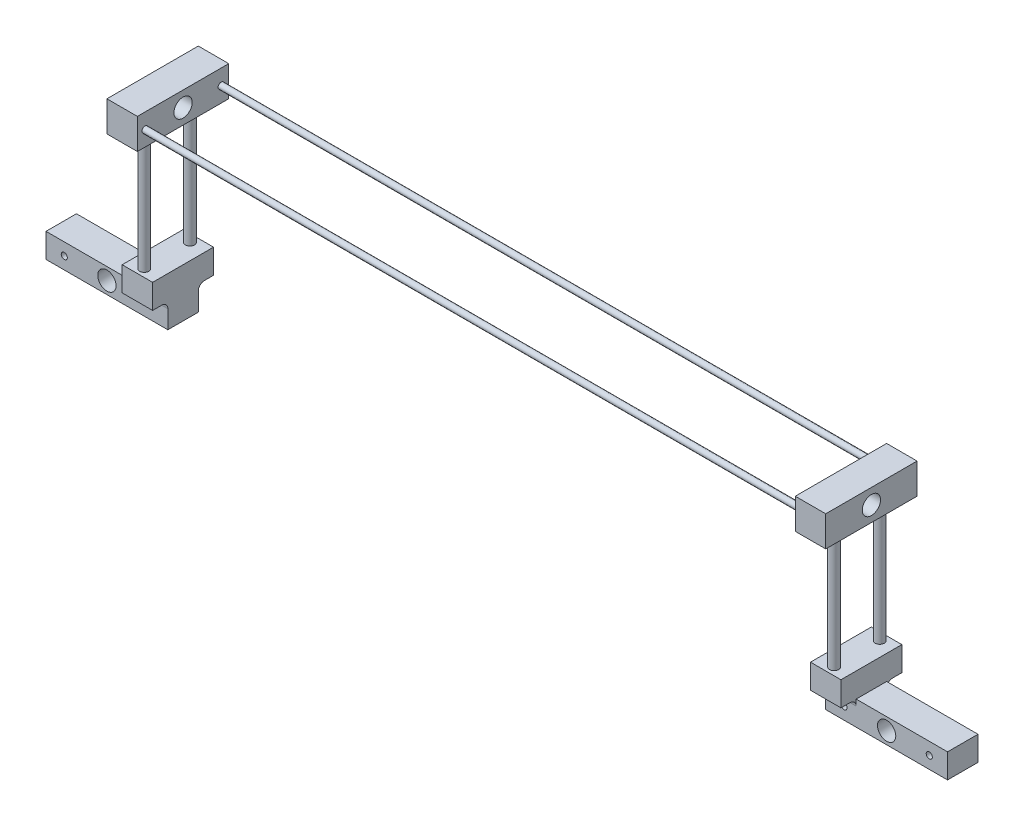
SolidWorks part; units mm, degrees
ref_plane "Front Plane" through (0, 0, 0) normal (0, 0, 1) x (1, 0, 0)
ref_plane "Top Plane" through (0, 0, 0) normal (0, 1, 0) x (1, 0, 0)
ref_plane "Right Plane" through (0, 0, 0) normal (1, 0, 0) x (0, 0, -1)
sketch "Sketch1" plane through (0, 0, 0) normal (0, 0, 1) x (1, 0, 0)
  line L0 (0, 0) -> (0, -345.7664) construction
  line L1 (0, 345.7664) -> (0, 0) construction
  line L3 (-740, -38.4289) -> (-540, -38.4289)
  line L4 (-740, -38.4289) -> (-740, -78.4289)
  line L5 (-740, -78.4289) -> (-540, -78.4289)
  line L6 (-540, -38.4289) -> (-540, -78.4289)
  line L10 (540, -38.4289) -> (580, -38.4289)
  line L11 (-540, -38.4289) -> (-580, -38.4289)
  line L15 (540, -38.4289) -> (540, -78.4289)
  line L16 (740, -78.4289) -> (540, -78.4289)
  line L17 (740, -38.4289) -> (740, -78.4289)
  line L18 (740, -38.4289) -> (540, -38.4289)
  circle A0 centre (-640, -58.4289) radius 15
  circle A1 centre (-570, -58.4289) radius 5
  circle A2 centre (-710, -58.4289) radius 5
  circle A3 centre (710, -58.4289) radius 5
  circle A4 centre (570, -58.4289) radius 5
  circle A5 centre (640, -58.4289) radius 15
  point P21 (0, 0)
  point P23 (-629.1463, -53.4025)
  dimension "D6" = 20
  dimension "D7" = 70
  dimension "D1" = 200
  dimension "D2" = 40
  dimension "D3" = 540
  dimension "D8" = 70
  dimension "D9" = 100
extrude "Boss-Extrude2" add sketch "Sketch1" along normal blind 50 contours L6 L3 L4 L5 A2 A1 A0 | L17 L18 L10 L15 L16 A4 A3 A5 region at (-660, -40.4685, 0) region at (560, -40.4685, 0)
sketch "Sketch2" plane through (0, -38.4289, 0) normal (0, 1, 0) x (1, 0, 0)
  line L0 (540, -50) -> (540, 0) construction
  line L2 (540, -25) -> (540, -75)
  line L3 (540, -75) -> (590, -75)
  line L4 (590, -25) -> (590, -75)
  line L7 (540, -25) -> (540, 25)
  line L8 (540, 25) -> (590, 25)
  line L9 (590, -25) -> (590, 25)
  line L15 (0, 604.6019) -> (0, -604.6019)
  line L20 (-590, -25) -> (-590, 25)
  line L21 (-540, 25) -> (-590, 25)
  line L22 (-540, -25) -> (-540, 25)
  line L23 (-590, -25) -> (-590, -75)
  line L28 (-540, -75) -> (-590, -75)
  line L29 (-540, -25) -> (-540, -75)
  circle A4 centre (566.2392, 12.5) radius 7.5
  circle A5 centre (566.2392, -62.5) radius 7.5
  circle A6 centre (-566.2392, -62.5) radius 7.5
  circle A7 centre (-566.2392, 12.5) radius 7.5
  point P23 (0, 0)
  point P34 (0, 0)
  dimension "D5" = 15
  dimension "D4" = 15
  dimension "D1" = 50
  dimension "D2" = 50
  dimension "D3" = 50
  dimension "D6" = 12.5
  dimension "D7" = 12.5
extrude "Boss-Extrude4" add sketch "Sketch2" along normal blind 40 contours L29 L22 L21 L20 L23 L28 A6 A7 | L4 L9 L0 | L0 L9 L8 L7 A4 | L2 L3 L4 L9 L8 L7 | A5 | A4 region at (564.9057, -38.4289, 25) region at (-564.9057, -38.4289, 25)
sketch "Sketch3" plane through (0, 0, 0) normal (0, 1, 0) x (1, 0, 0)
  circle A0 centre (-566.2392, 12.5) radius 7.5
  circle A1 centre (-566.2392, -62.5) radius 7.5
  circle A2 centre (566.2392, 12.5) radius 7.5
  circle A3 centre (566.2392, -62.5) radius 7.5
extrude "Boss-Extrude5" add sketch "Sketch3" along normal blind 250 and the other way blind 40
sketch "Sketch4" plane through (0, 250, 0) normal (0, 1, 0) x (1, 0, 0)
  line L0 (-540, 25) -> (-590, 25) construction
  line L1 (590, -75) -> (540, -75)
  line L2 (590, -75) -> (590, 25)
  line L3 (590, 25) -> (540, 25)
  line L4 (540, -75) -> (540, 25)
  line L5 (-540, -75) -> (-590, -75)
  line L6 (-540, -75) -> (-540, 25)
  line L7 (-540, 25) -> (-590, 25)
  line L8 (-590, -75) -> (-590, 25)
  circle A0 centre (566.2392, -62.5) radius 7.5
  circle A1 centre (566.2392, 12.5) radius 7.5
  circle A2 centre (-566.2392, -62.5) radius 7.5
  circle A3 centre (-566.2392, 12.5) radius 7.5
extrude "Boss-Extrude6" add sketch "Sketch4" against normal blind 50 contours L2 L1 L4 L3 | L6 L5 L8 L7
sketch "Sketch5" plane through (-590, 0, 0) normal (-1, 0, 0) x (0, 0, 1)
  line L0 (-25, 200) -> (-25, 250) construction
  line L1 (75, 200) -> (-25, 200) construction
  circle A0 centre (25, 225) radius 15
  dimension "D1" = 50
  dimension "D2" = 25
extrude "Cut-Extrude1" cut sketch "Sketch5" against normal blind 1180
sketch "Sketch6" plane through (0, 250, 0) normal (0, 1, 0) x (1, 0, 0)
  line L0 (0, -294.9316) -> (0, 294.9316)
  line L1 (540, -75) -> (590, -75)
  line L2 (540, -75) -> (540, -100)
  line L3 (540, -100) -> (590, -100)
  line L4 (590, -75) -> (590, -100)
  line L5 (540, 25) -> (590, 25)
  line L6 (540, 25) -> (540, 50)
  line L7 (540, 50) -> (590, 50)
  line L8 (590, 25) -> (590, 50)
  line L9 (-590, 25) -> (-590, 50)
  line L10 (-540, 50) -> (-590, 50)
  line L11 (-540, 25) -> (-540, 50)
  line L12 (-540, 25) -> (-590, 25)
  line L13 (-590, -75) -> (-590, -100)
  line L14 (-540, -100) -> (-590, -100)
  line L15 (-540, -75) -> (-540, -100)
  line L16 (-540, -75) -> (-590, -75)
  point P10 (540, 37.5)
  point P15 (0, 0)
  line M4 (590, 25) -> (540, 25)
  line M6 (540, -75) -> (590, -75)
  dimension "D1" = 25
  dimension "D2" = 25
extrude "Boss-Extrude8" add sketch "Sketch6" against normal blind 50 contours L4 L2 L3 M6 | L8 L7 L6 M4 | L15 L16 L13 L14 | L12 L11 L10 L9 region at (565, 250, 87.5) region at (565, 250, -37.5) region at (-565, 250, -37.5) region at (-565, 250, 87.5)
sketch "Sketch7" plane through (-590, 0, 0) normal (-1, 0, 0) x (0, 0, 1)
  line L0 (100, 200) -> (100, 250) construction
  line L1 (-50, 200) -> (-50, 250) construction
  line L2 (100, 250) -> (-50, 250) construction
  line L3 (100, 200) -> (-50, 200) construction
  circle A0 centre (87.5, 225) radius 5
  circle A1 centre (-37.5, 225) radius 5
  dimension "D2" = 25
  dimension "D1" = 12.5
  dimension "12.5" = 12.5
  dimension "D3" = 25
extrude "Boss-Extrude9" add sketch "Sketch7" against normal blind 1180
fillet "Fillet1" radius 10 4 edges at (-565, -38.4289, 0) (-565, -38.4289, 50) (565, -38.4289, 50) (565, -38.4289, 0)
